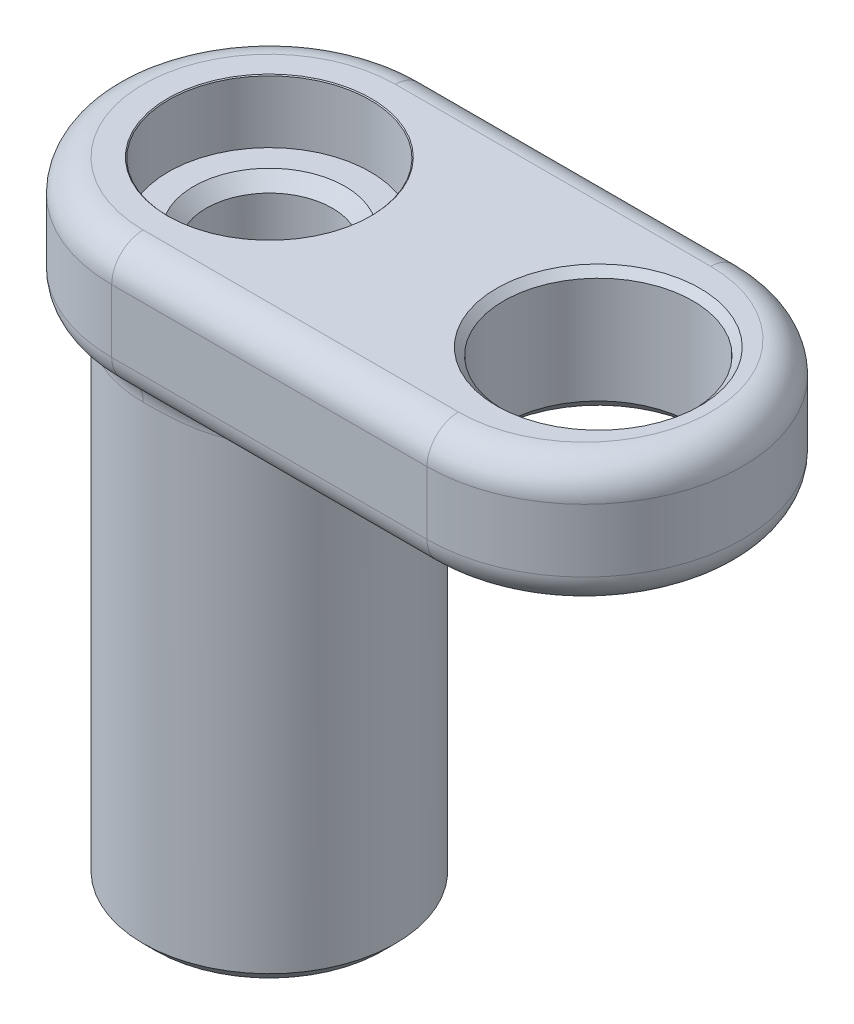
SolidWorks part; units mm, degrees
ref_plane "Front Plane" through (0, 0, 0) normal (0, 0, 1) x (1, 0, 0)
ref_plane "Top Plane" through (0, 0, 0) normal (0, 1, 0) x (1, 0, 0)
ref_plane "Right Plane" through (0, 0, 0) normal (1, 0, 0) x (0, 0, -1)
sketch "Sketch1" plane through (0, 0, 0) normal (0, 1, 0) x (1, 0, 0)
  circle A0 centre (0, 0) radius 20
  dimension "D1" = 40
extrude "Boss-Extrude1" add sketch "Sketch1" along normal blind 100
sketch "Sketch2" plane through (0, 100, 0) normal (0, 1, 0) x (1, 0, 0)
  line L0 (0, 0) -> (50, 0) construction
  line L1 (0, 25) -> (50, 25)
  line L2 (0, -25) -> (50, -25)
  arc A0 (0, 25) -> (0, -25) centre (0, 0) ccw
  arc A1 (50, -25) -> (50, 25) centre (50, 0) ccw
  point P3 (25, 0)
  dimension "D2" = 25
  dimension "D1" = 50
extrude "Boss-Extrude2" add sketch "Sketch2" against normal blind 20
hole_wizard "CBORE for M5 Hex Head Bolt1" positions "Sketch12" profile "Sketch13" counterbore size "M5" standard "ISO" end condition through all
sketch "Sketch12" plane through (0, 100, 0) normal (0, 1, 0) x (1, 0, 0)
  point P0 (0, 0)
sketch "Sketch13" plane through (0, 100, 0) normal (1, 0, 0) x (0, 0, 1)
  line L0 (0, 0) -> (0, 100)
  line L1 (0, 100) -> (10, 100)
  line L3 (10, 100) -> (10, 10)
  line L4 (16, 10) -> (10, 10)
  line L5 (16, 10) -> (16, 0.144)
  line L6 (16, 0.144) -> (16.144, 0)
  line L7 (16.144, 0) -> (0, 0)
  line L8 (-16, 0.144) -> (-16.144, 0) construction
  line L11 (0, -6.35) -> (0, 107.95) construction
  dimension "Thru Hole Dia." = 20
  dimension "Thru Hole Depth" = 100
  dimension "C'Bore Dia." = 32
  dimension "C'Bore Depth" = 10
  dimension "Near C'Sink Dia." = 32.288
  dimension "Near C'Sink Angle" = 90
hole_wizard "Ø1.0mm Dowel Hole1" positions "Sketch14" profile "Sketch15" hole size "Ø1.0" standard "ISO" end condition through all
sketch "Sketch14" plane through (0, 100, 0) normal (0, 1, 0) x (1, 0, 0)
  point P0 (52.1675, 0)
sketch "Sketch15" plane through (52.1675, 100, 0) normal (1, 0, 0) x (0, 0, 1)
  line L0 (0, 0) -> (0, 100)
  line L1 (0, 100) -> (15, 100)
  line L2 (15, 100) -> (15, 1.144)
  line L3 (15, 1.144) -> (16.144, 0)
  line L5 (16.144, 0) -> (0, 0)
  line L6 (-15, 1.144) -> (-16.144, 0) construction
  line L11 (0, -6.35) -> (0, 107.95) construction
  dimension "Thru Hole Dia." = 30
  dimension "Thru Hole Depth" = 100
  dimension "Near C'Sink Dia." = 32.288
  dimension "Near C'Sink Angle" = 90
chamfer "Chamfer9" distance 2 angle 45 1 edges at (0, 0, 10) tangent propagation no
chamfer "Chamfer10" distance 2 angle 45 1 edges at (52.1675, 80, 15) tangent propagation no
chamfer "Chamfer11" distance 2 angle 45 1 edges at (0, 90, 10)
fillet "Fillet1" radius 5 4 edges at (25, 100, -25) (75, 100, 0) (25, 100, 25) (-25, 100, 0)
fillet "Fillet2" radius 5 4 edges at (25, 80, 25) (-25, 80, 0) (25, 80, -25) (75, 80, 0)
fillet "Fillet3" radius 5 2 edges at (-20, 80, 0) (20, 80, 0)
chamfer "Chamfer12" distance 2 angle 45 1 edges at (0, 0, 20)
